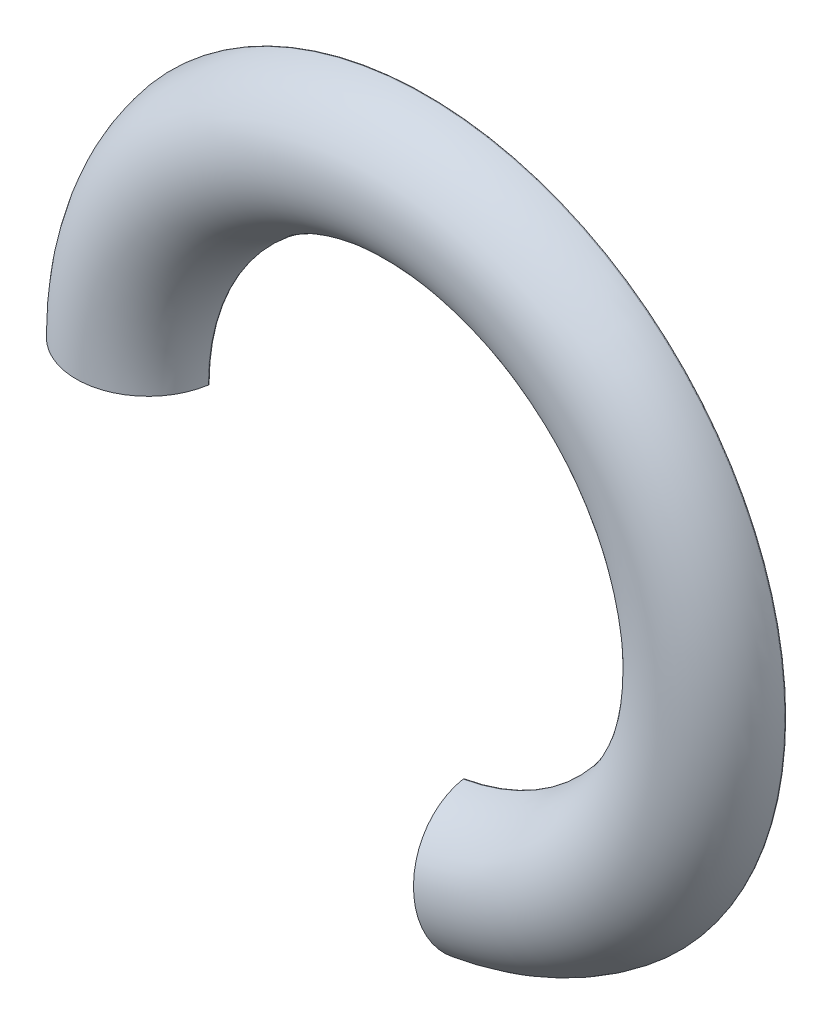
SolidWorks part; units mm, degrees
ref_plane "Front Plane" through (0, 0, 0) normal (0, 0, 1) x (1, 0, 0)
ref_plane "Top Plane" through (0, 0, 0) normal (0, 1, 0) x (1, 0, 0)
ref_plane "Right Plane" through (0, 0, 0) normal (1, 0, 0) x (0, 0, -1)
ref_axis "Polar Axis" through (0, 0, -81.2751) along (0, 0, 1)
ref_axis "Solar Axis" through (-89.4943, 0, 0) along (1, 0, 0)
sketch "Belt Path" plane through (0, 0, 0) normal (0, 0, 1) x (1, 0, 0)
  circle A2 centre (0, 0) radius 42
  dimension "D1" = 84
sketch "Belt Profile" plane through (0, 0, 0) normal (0, 1, 0) x (1, 0, 0)
  line L0 (-32.9402, -1.4) -> (-31.825, -1.4)
  line L1 (-42, 0) -> (42, 0) construction
  line L2 (-42, 0) -> (42, 0) construction
  line L3 (-56.7846, 0) -> (-56.7846, -0.8) construction
  line L4 (-52.175, -1.4) -> (-51.0598, -1.4)
  line L5 (-42, 0) -> (-42, -9) construction
  line L6 (-56.7846, -0.8) -> (-58.0457, -0.8) construction
  line L7 (-42, 0) -> (-42, 1.5) construction
  line L11 (-53.5, 0) -> (-58.0457, 0) construction
  line L17 (-51, 0.2) -> (-51, -1.1) construction
  line L22 (-52.7774, -1.4) -> (-52.7774, -3.1) construction
  line L23 (-55.663, -0.5) -> (-55.663, -2.9) construction
  line L24 (-51.3, -1.4) -> (-52.7774, -1.4) construction
  line L25 (-55.163, -3.4) -> (-53.0774, -3.4) construction
  line L26 (-55.163, 0) -> (-52.4981, 0) construction
  line L27 (-53.5, 1.4) -> (-58.0457, 1.4) construction
  line L28 (-53, 0.5) -> (-53, 0.9) construction
  arc A0 (-52.3725, -1.6311) -> (-31.6275, -1.6311) centre (-42, 0) ccw
  arc A1 (-50.8628, -1.5652) -> (-33.1372, -1.5652) centre (-42, 0) ccw
  arc A2 (-32.9402, -1.4) -> (-33.1372, -1.5652) centre (-32.9402, -1.6) ccw
  arc A3 (-31.825, -1.4) -> (-31.6275, -1.6311) centre (-31.825, -1.6) cw
  arc A4 (-51.0598, -1.4) -> (-50.8628, -1.5652) centre (-51.0598, -1.6) cw
  arc A5 (-50.7827, 2.1659) -> (-51, 0.2) centre (-42, 0.2) ccw construction
  arc A6 (-52.3725, -1.6311) -> (-52.175, -1.4) centre (-52.175, -1.6) cw
  arc A12 (-55.663, -2.9) -> (-55.163, -3.4) centre (-55.163, -2.9) ccw construction
  arc A13 (-52.7774, -3.1) -> (-53.0774, -3.4) centre (-53.0774, -3.1) cw construction
  arc A14 (-53, 0.9) -> (-53.5, 1.4) centre (-53.5, 0.9) ccw construction
  arc A15 (-55.163, 0) -> (-55.663, -0.5) centre (-55.163, -0.5) ccw construction
  arc A16 (-52.1577, 2.8591) -> (-52.4981, 0) centre (-42, 0.2) ccw construction
  arc A17 (-51.3, -1.4) -> (-51, -1.1) centre (-51.3, -1.1) ccw construction
  arc A18 (-53, 0.5) -> (-53.5, 0) centre (-53.5, 0.5) cw construction
  point P0 (-65, 0)
  point P2 (-54, 0)
  point P3 (-65, 0)
  point P9 (-52.568, 3.8008)
  point P29 (-52.4062, -1.4)
  dimension "D1" = 42
  dimension "D2" = 1.4
  dimension "D3" = 21
  dimension "D7" = 0.2
  dimension "D5" = 1.5
  dimension "D4" = 1.5
  dimension "D6" = 1.4
sweep "Main Belt" add profiles "Belt Profile" path "Belt Path"
sketch "Test Cutout Sketch" plane through (0, 0, 0) normal (0, 0, 1) x (1, 0, 0)
  line L0 (0, 0) -> (10.4189, -59.0885)
  line L1 (0, 0) -> (-60, 0)
  arc A0 (-60, 0) -> (10.4189, -59.0885) centre (0, 0) ccw
  dimension "D1" = 60
  dimension "D2" = 100
extrude "Cutout" cut sketch "Test Cutout Sketch" against normal through all and the other way through all
